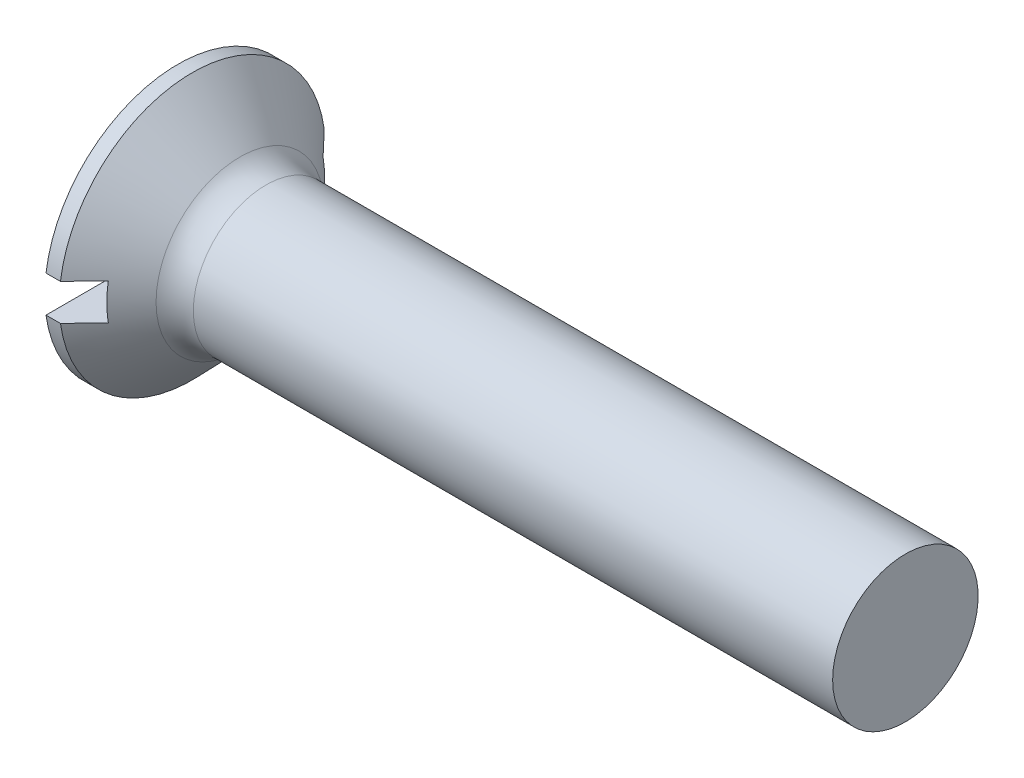
SolidWorks part; units mm, degrees
ref_plane "Front Plane" through (0, 0, 0) normal (0, 0, 1) x (1, 0, 0)
ref_plane "Top Plane" through (0, 0, 0) normal (0, 1, 0) x (1, 0, 0)
ref_plane "Right Plane" through (0, 0, 0) normal (1, 0, 0) x (0, 0, -1)
sketch "BodySke" plane through (0, 0, 0) normal (0, 0, 1) x (1, 0, 0)
  line L0 (0, 0) -> (111.3824, 0) construction
  line L1 (0, 0) -> (0, 9.15)
  line L2 (0, 9.15) -> (0.9924, 9.15)
  line L3 (0.9924, 9.15) -> (5, 5)
  line L4 (5, 5) -> (50, 5)
  line L5 (50, 5) -> (50, 0)
  line L6 (6.5, 8.824) -> (6.5, -5.8939) construction
  line L7 (0, 0) -> (50, 0)
  line L8 (12, 8.824) -> (12, -4.958) construction
  line L9 (0, -9.15) -> (0.9924, -9.15) construction
  line L10 (0.9924, -9.15) -> (5, -5) construction
  line L11 (5, -5) -> (50, -5) construction
  point P10 (50, 4.172)
  dimension "Thread_minor" = 8.344
  dimension "Length" = 50
  dimension "Head_height" = 5
  dimension "Head_dia" = 18.3
  dimension "Advance" = 1.5
  dimension "Thread_length" = 38
revolve "BaseBody" add sketch "BodySke" angle 360 about L0
cosmetic thread "ThreadCosmetic" [suppressed] parameters "Thread_length"=38, "Thread_minor"=8.344
fillet "Fillet1" radius 2.5 1 edges at (5, 0, 5)
sketch "SlotSke" plane through (0, 0, 0) normal (-1, 0, 0) x (0, 0, 1)
  line L1 (-9.15, 1.25) -> (9.15, 1.25)
  line L2 (-9.15, 1.25) -> (-9.15, -1.25)
  line L3 (-9.15, -1.25) -> (9.15, -1.25)
  line L4 (9.15, 1.25) -> (9.15, -1.25)
  dimension "D1" = 18.3
  dimension "D2" = 9.15
  dimension "D3" = 1.25
extrude "Slot" cut sketch "SlotSke" against normal blind 2.6
sketch "ThdSchSke" plane through (0, 0, 0) normal (0, 0, 1) x (1, 0, 0)
  line L0 (0, 0) -> (55.1256, 0) construction
  line L1 (0, 0) -> (111.3824, 0) construction
  line L2 (49.522, 5) -> (49.522, 5.9561)
  line L3 (49.522, 5.9561) -> (50.478, 5.9561)
  line L4 (50.478, 5.9561) -> (50.478, 5)
  line L5 (50.478, 5) -> (50, 4.172)
  line L6 (50, 4.172) -> (49.522, 5)
  line L7 (5, 5) -> (50, 5) construction
  line L13 (50, 5) -> (50, 0) construction
revolve "ThreadSchematic" [suppressed] cut sketch "ThdSchSke" angle 360 about L0
pattern_linear "ThdSchPat" [suppressed] count 26 along (-1, 0, 0) of bodies 103
equation "\"Thread_minor@ThreadCosmetic\" = \"Thread_minor@BodySke\""
equation "\"Thread_length@ThreadCosmetic\" = \"Thread_length@BodySke\""
equation "\"D1@SlotSke\" = \"Head_dia@BodySke\""
equation "\"D2@SlotSke\" = \"D1@SlotSke\" / 2"
equation "\"D3@SlotSke\" = \"Slot_width@SlotSke\" / 2"
equation "\"Advance@ThdSchPat\" = \"Advance@BodySke\""
equation "\"D1@ThdSchPat\" =  int( \"Thread_length@BodySke\" / \"Advance@ThdSchPat\" )   + 1"
